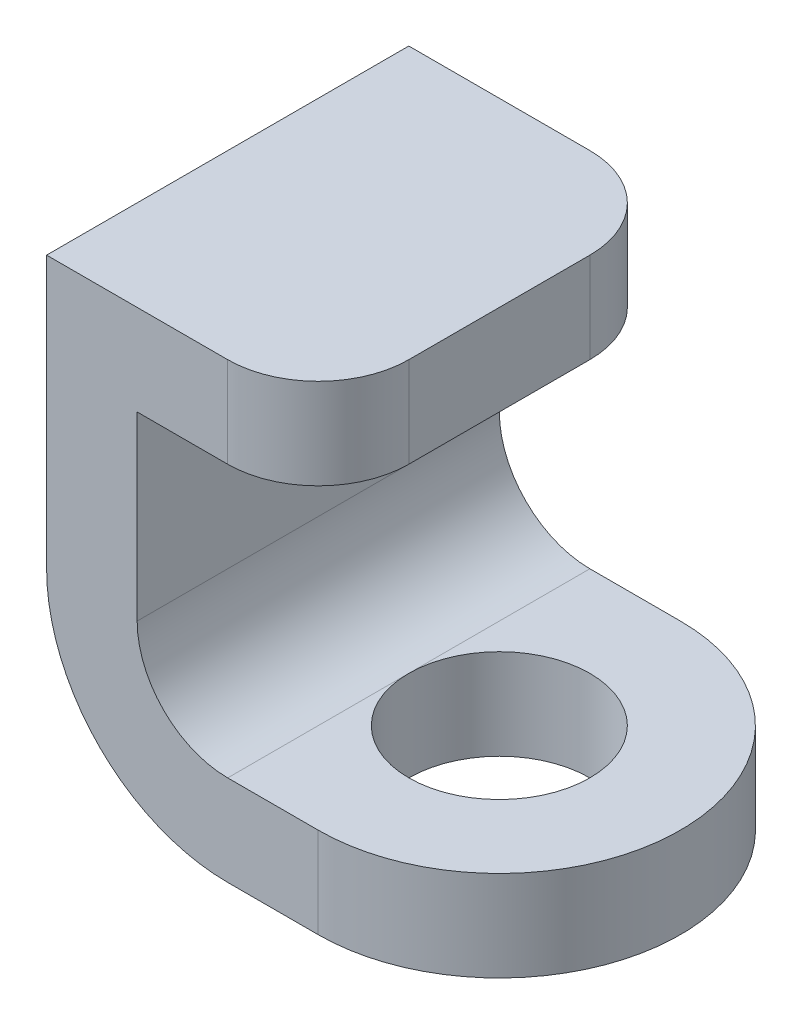
SolidWorks part; units mm, degrees
ref_plane "前基準面" through (0, 0, 0) normal (0, 0, 1) x (1, 0, 0)
ref_plane "上基準面" through (0, 0, 0) normal (0, 1, 0) x (1, 0, 0)
ref_plane "右基準面" through (0, 0, 0) normal (1, 0, 0) x (0, 0, -1)
sketch "草圖1" plane through (0, 0, 0) normal (0, 1, 0) x (1, 0, 0)
  line L0 (0, 2) -> (-3, 2)
  line L1 (-3, 2) -> (-3, -2)
  line L2 (-3, -2) -> (0, -2)
  line L3 (0, -2) -> (-2, -2)
  line L4 (-2, -2) -> (-2, 2)
  circle A0 centre (0, 0) radius 1
  arc A1 (0, -2) -> (0, 2) centre (0, 0) ccw
  dimension "D1" = 4
  dimension "D2" = 2
  dimension "D3" = 3
  dimension "D4" = 1
extrude "填料-伸長1" add sketch "草圖1" along normal blind 1 contours L2 A1 L0 L4 A0 region at (1.9434, 0, 0)
extrude "填料-伸長2" add sketch "草圖1<3>" along normal blind 5 contours L2 L4 L0 L1 region at (-2.5, 0, 0)
sketch "草圖1<3>" plane through (0, 0, 0) normal (0, 1, 0) x (1, 0, 0) same geometry as "草圖1"
sketch "草圖2" plane through (-2, 0, 0) normal (1, 0, 0) x (0, 0, -1)
  line L0 (2, 5) -> (2, 1) construction
  line L1 (-2, 5) -> (2, 5)
  line L2 (-2, 5) -> (-2, 4)
  line L3 (-2, 4) -> (2, 4)
  line L4 (2, 5) -> (2, 4)
  dimension "D1" = 1
extrude "填料-伸長3" add sketch "草圖2" along normal blind 2
fillet "圓角1" radius 1 2 edges at (0, 4.5, -2) (0, 4.5, 2)
fillet "圓角2" radius 2 1 edges at (-3, 0, 0)
fillet "圓角3" radius 1 1 edges at (-2, 1, 0)
